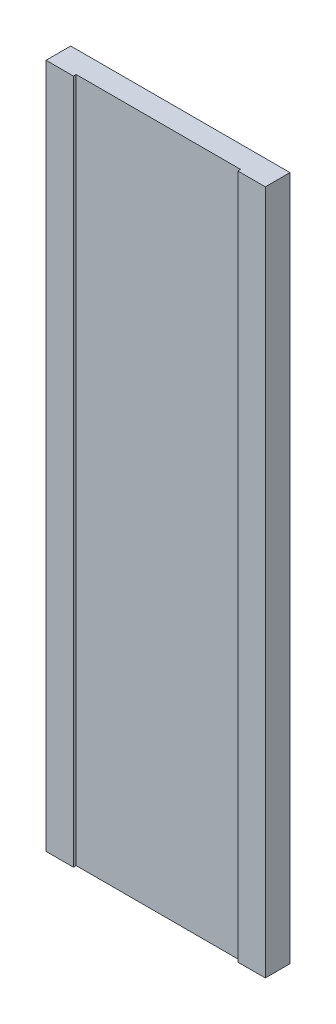
SolidWorks part; units mm, degrees
ref_plane "Alzado" through (0, 0, 0) normal (0, 0, 1) x (1, 0, 0)
ref_plane "Planta" through (0, 0, 0) normal (0, 1, 0) x (1, 0, 0)
ref_plane "Vista lateral" through (0, 0, 0) normal (1, 0, 0) x (0, 0, -1)
sketch "Croquis1" plane through (0, 0, 0) normal (0, 0, 1) x (1, 0, 0)
  line L1 (0, 0) -> (80, 0)
  line L2 (0, 0) -> (0, 250)
  line L3 (0, 250) -> (80, 250)
  line L4 (80, 0) -> (80, 250)
  dimension "D1" = 250
  dimension "D2" = 80
extrude "Saliente-Extruir1" add sketch "Croquis1" along normal blind 8
sketch "Croquis2" plane through (0, 0, 8) normal (0, 0, 1) x (1, 0, 0)
  line L0 (80, 250) -> (0, 250) construction
  line L1 (0, 0) -> (10, 0)
  line L2 (0, 0) -> (0, 250)
  line L3 (0, 250) -> (10, 250)
  line L4 (10, 0) -> (10, 250)
  line L6 (80, 0) -> (70, 0)
  line L7 (80, 0) -> (80, 250)
  line L8 (80, 250) -> (70, 250)
  line L9 (70, 0) -> (70, 250)
  dimension "D1" = 10
  dimension "D2" = 10
extrude "Saliente-Extruir2" add sketch "Croquis2" along normal blind 1
